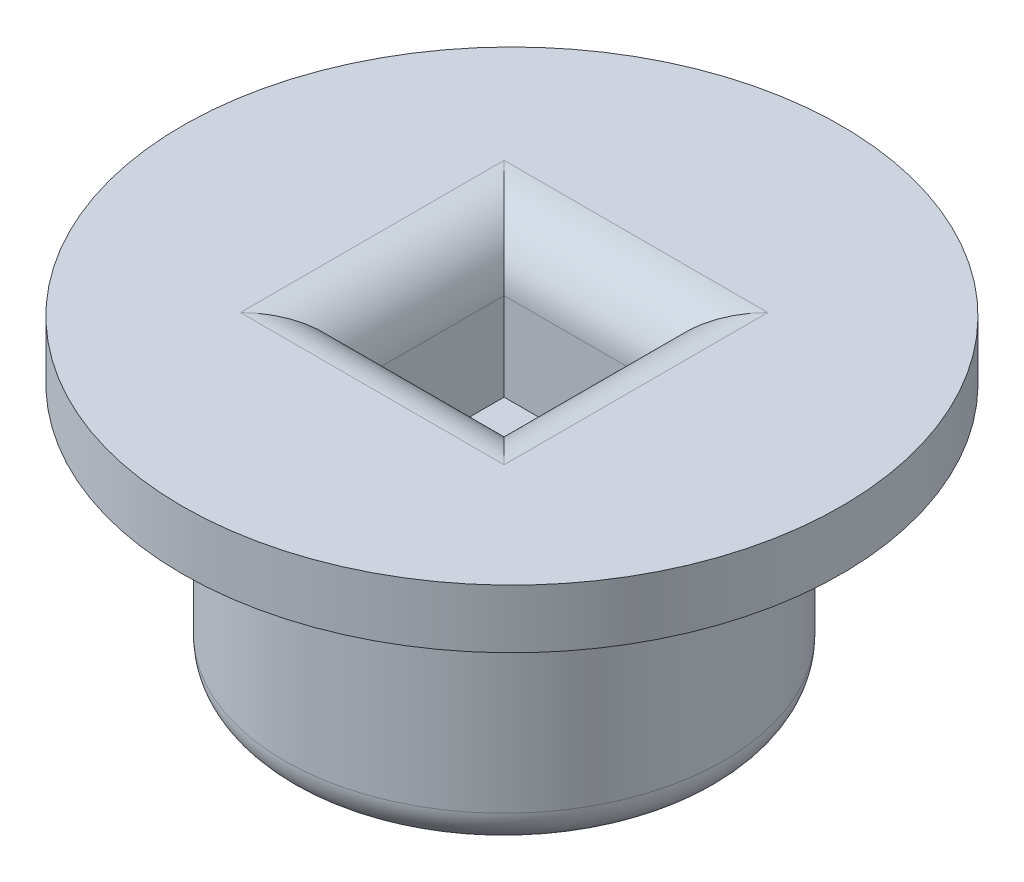
SolidWorks part; units mm, degrees
ref_plane "前视基准面" through (0, 0, 0) normal (0, 0, 1) x (1, 0, 0)
ref_plane "上视基准面" through (0, 0, 0) normal (0, 1, 0) x (1, 0, 0)
ref_plane "右视基准面" through (0, 0, 0) normal (1, 0, 0) x (0, 0, -1)
sketch "草图1" plane through (0, 0, 0) normal (0, 1, 0) x (1, 0, 0)
  circle A0 centre (0, 0) radius 3
  dimension "D1" = 6
extrude "凸台-拉伸1" add sketch "草图1" along normal blind 3.5 contours A0
sketch "草图2" plane through (0, 3.5, 0) normal (0, 1, 0) x (1, 0, 0)
  circle A0 centre (0.0949, 0.012) radius 4.5
  dimension "D1" = 9
extrude "凸台-拉伸2" add sketch "草图2" along normal blind 0.8
sketch "草图4" plane through (0, 4.3, 0) normal (0, 1, 0) x (1, 0, 0)
  line L1 (1, -1) -> (-1, -1)
  line L2 (1, -1) -> (1, 1)
  line L3 (1, 1) -> (-1, 1)
  line L4 (-1, -1) -> (-1, 1)
  line L5 (1, -1) -> (-1, 1) construction
  line L6 (1, 1) -> (-1, -1) construction
  circle A0 centre (0, 0) radius 3 construction
  point P0 (0, 0)
  dimension "D1" = 2
  dimension "D2" = 2
extrude "切除-拉伸1" cut sketch "草图4" against normal blind 2
fillet "圆角1" radius 0.5 1 edges at (0, 0, 3)
fillet "圆角2" radius 0.8 4 edges at (0, 4.3, 1) (-1, 4.3, 0) (0, 4.3, -1) (1, 4.3, 0)
